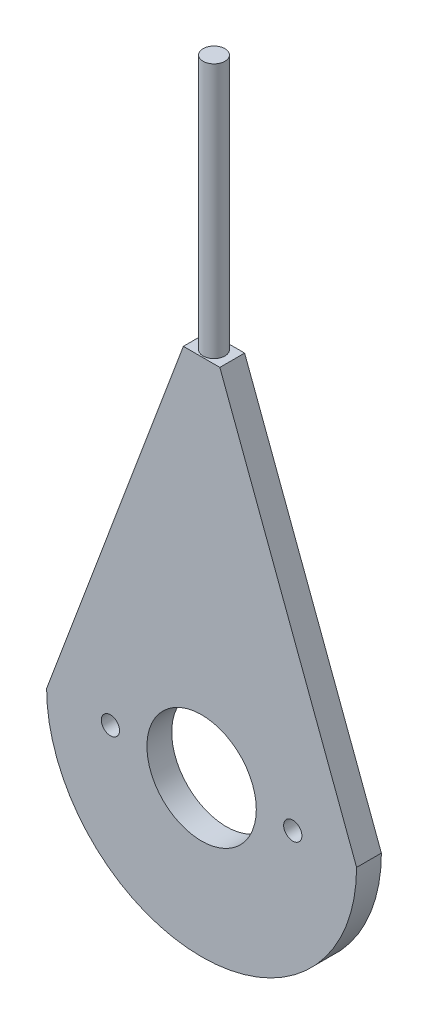
SolidWorks part; units mm, degrees
material "1060 Alloy"
ref_plane "Front Plane" through (0, 0, 0) normal (0, 0, 1) x (1, 0, 0)
ref_plane "Top Plane" through (0, 0, 0) normal (0, 1, 0) x (1, 0, 0)
ref_plane "Right Plane" through (0, 0, 0) normal (1, 0, 0) x (0, 0, -1)
sketch "Sketch1" plane through (0, 0, 0) normal (0, 0, 1) x (1, 0, 0)
  line L0 (-42.5, 0) -> (42.5, 0) construction
  line L1 (-42.5, 0) -> (-5, 100)
  line L2 (5, 100) -> (42.5, 0)
  line L3 (0, 0) -> (0, 100) construction
  line L4 (-5, 100) -> (5, 100)
  arc A0 (-42.5, 0) -> (42.5, 0) centre (0, 0) ccw
  circle A1 centre (0, 0) radius 15
  circle A2 centre (25, 0) radius 2.5
  circle A3 centre (-25, 0) radius 2.5
  dimension "D4" = 30
  dimension "D5" = 5
  dimension "D1" = 85
  dimension "D2" = 10
  dimension "D3" = 100
  dimension "D6" = 25
base flange "Base-Flange1" sketch "Sketch1" thickness 6.8 reverse thickness direction no parameters "D1"=0.7366
sketch "Sketch6" plane through (0, 100, 0) normal (0, 1, 0) x (1, 0, 0)
  line L0 (5, 6.8) -> (-5, 0) construction
  circle A0 centre (0, 3.4) radius 3
  dimension "D1" = 6
extrude "Boss-Extrude1" add sketch "Sketch6" along normal blind 70
sketch "Bend-Lines1" [suppressed] plane through (0, 0, 0) normal (0, 1, 0) x (1, 0, 0)
sketch "Bounding-Box1" [suppressed] plane through (0, 0, 0) normal (0, 1, 0) x (1, 0, 0)
sheet metal parameters "Sheet-Metal1" thickness 6.8 parameters "D1"=0.7366
flat pattern "Flat-Pattern1" [suppressed]
sketch "Bend-Lines2" plane through (0, 0, 0) normal (0, 1, 0) x (1, 0, 0)
sketch3d "Bounding-Box2" [suppressed]
  line L0 (-3.7671, 103.2877, 0) -> (-52.183, -25.8214, 0) construction
  line L1 (73.2871, 74.3923, 0) -> (24.8712, -54.7167, 0) construction
  line L2 (-3.7671, 103.2877, 0) -> (73.2871, 74.3923, 0) construction
  line L3 (-52.183, -25.8214, 0) -> (24.8712, -54.7167, 0) construction
sheet metal parameters "Sheet-Metal2" thickness 6.8 parameters "D1"=0.7366
flat pattern "Flat-Pattern1"
sketch "Bend-Lines2" plane through (0, 0, 0) normal (0, 1, 0) x (1, 0, 0)
sketch3d "Bounding-Box2" [suppressed]
  line L0 (3.7671, 103.2877, 0) -> (52.183, -25.8214, 0) construction
  line L1 (-73.2871, 74.3923, 0) -> (-24.8712, -54.7167, 0) construction
  line L2 (3.7671, 103.2877, 0) -> (-73.2871, 74.3923, 0) construction
  line L3 (52.183, -25.8214, 0) -> (-24.8712, -54.7167, 0) construction
